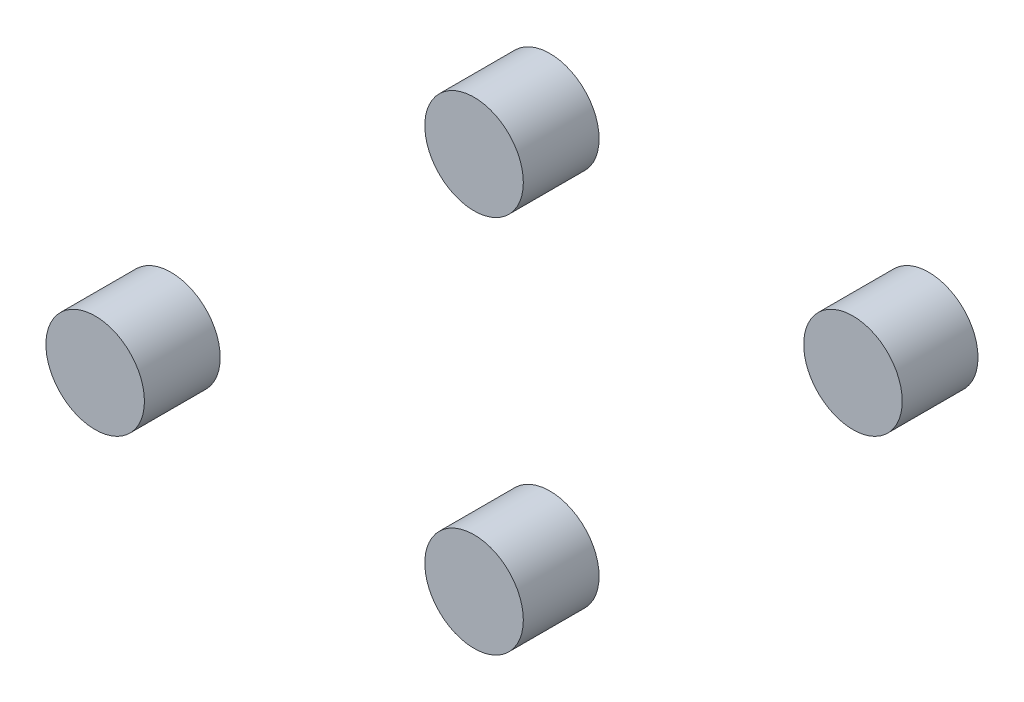
SolidWorks part; units mm, degrees
ref_plane "Front" through (0, 0, 0) normal (0, 0, 1) x (1, 0, 0)
ref_plane "Top" through (0, 0, 0) normal (0, 1, 0) x (1, 0, 0)
ref_plane "Right" through (0, 0, 0) normal (1, 0, 0) x (0, 0, -1)
sketch "Sketch1" plane through (0, 0, 0) normal (0, 0, 1) x (1, 0, 0)
  line L0 (180.9007, 0) -> (-180.9007, 0) construction
  circle A0 centre (0, 0) radius 49.53
  circle A1 centre (381, 0) radius 49.53
  dimension "D1" = 99.06
  dimension "D2" = 381
extrude "Boss-Extrude1" add sketch "Sketch1" against normal blind 76.2 from offset 228.6
mirror "Mirror3" about plane through (0, 0, 0) normal (0, 0, 1) of bodies 101 102
